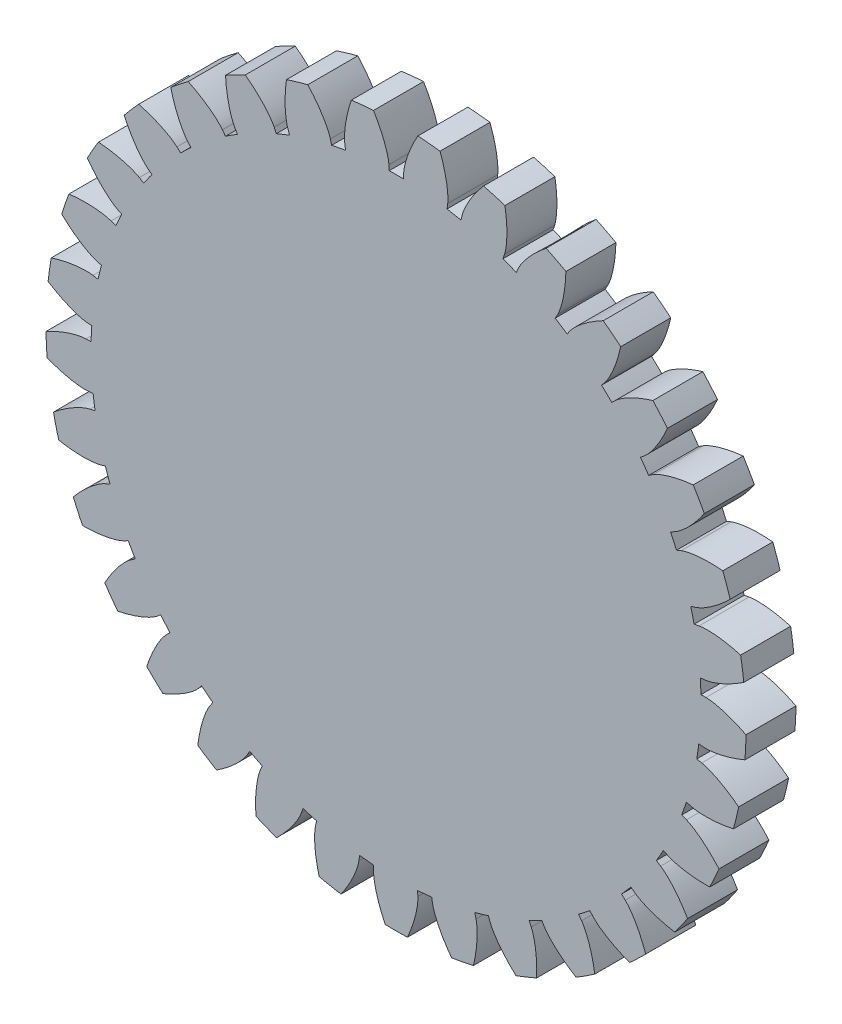
SolidWorks part; units mm, degrees
ref_plane "Спереди" through (0, 0, 0) normal (0, 0, 1) x (1, 0, 0)
ref_plane "Сверху" through (0, 0, 0) normal (0, 1, 0) x (1, 0, 0)
ref_plane "Справа" through (0, 0, 0) normal (1, 0, 0) x (0, 0, -1)
sketch "Эскиз2" plane through (0, 0, 0) normal (0, 0, 1) x (1, 0, 0)
  line L0 (0, 51.1792) -> (0, -43.95) construction
  line L1 (10.2103, 62.2838) -> (97.1798, 30.6294) construction
  line L2 (-13.5021, 66) -> (13.4511, 66) construction
  line L3 (1.5272, 62.0009) -> (1.4926, 60.9817)
  line L6 (-1.4156, 62.0036) -> (-1.3545, 60.985)
  circle A0 centre (0, 0) radius 70
  circle A1 centre (0, 0) radius 66 construction
  circle A2 centre (0, 0) radius 62.0197 construction
  circle A3 centre (0, 0) radius 61
  spline S0 degree 4 poles (1.5272, 62.0009) (1.529, 62.0517) (1.5344, 62.1533) (1.5532, 62.3559) (1.6041, 62.7397) (1.6972, 63.2512) (1.8619, 63.96) (2.1064, 64.81) (2.5522, 66.1188) (3.2996, 67.8941) (4.5374, 70.2843) (6.4126, 73.1886) (8.7564, 76.1773) (11.5565, 79.1636) (14.5826, 81.9194) (17.7987, 84.45) (21.3429, 86.8747) (25.9214, 89.5789) (31.6296, 92.3487) (38.5319, 94.9353) (46.4475, 97.0389) (53.5119, 98.2365) (59.6214, 98.8253) (64.7297, 99.035) (68.8201, 99.0381) (72.9067, 98.8812) (76.9854, 98.5675) (82.0635, 97.986) (88.1211, 96.9899) (95.1032, 95.4154) (101.4808, 93.5105) (106.2939, 91.812) (109.6398, 90.5071) (111.5036, 89.7481) (113.2806, 88.9869) (114.7009, 88.3604) (116.3483, 87.6041) (117.2223, 87.1924) (118.4723, 86.592) (119.4783, 86.0939) (120.646, 85.5087) (121.8873, 84.8664) (123.3709, 84.0795) (124.8011, 83.2956) (126.0714, 82.5816) (127.1351, 81.9677) (127.8524, 81.5474) (128.2039, 81.3388) (128.3825, 81.2327) knots 0 0 0 0 0 0.001401 0.002802 0.005604 0.010661 0.015718 0.022839 0.02996 0.048734 0.068727 0.096889 0.125051 0.153212 0.181374 0.209535 0.237696 0.271429 0.327752 0.384075 0.440398 0.496721 0.524883 0.553044 0.581206 0.609367 0.637529 0.66569 0.722013 0.778336 0.834659 0.84874 0.86282 0.876901 0.890982 0.900036 0.909091 0.920455 0.926136 0.931818 0.943182 0.954545 0.965909 0.977273 0.988636 0.994318 1 1 1 1 1 construction
  spline S1 degree 4 poles (1.5272, 62.0009) (1.529, 62.0517) (1.5344, 62.1533) (1.5532, 62.3559) (1.6041, 62.7397) (1.6972, 63.2512) (1.8619, 63.96) (2.1064, 64.81) (2.5522, 66.1188) (3.2996, 67.8941) (4.5374, 70.2843) (6.4126, 73.1886) (8.7564, 76.1773) (11.5565, 79.1636) (14.5826, 81.9194) (17.7987, 84.45) (21.3429, 86.8747) (25.9214, 89.5789) (31.6296, 92.3487) (38.5319, 94.9353) (46.4475, 97.0389) (53.5119, 98.2365) (59.6214, 98.8253) (64.7297, 99.035) (68.8201, 99.0381) (72.9067, 98.8812) (76.9854, 98.5675) (82.0635, 97.986) (88.1211, 96.9899) (95.1032, 95.4154) (101.4808, 93.5105) (106.2939, 91.812) (109.6398, 90.5071) (111.5036, 89.7481) (113.2806, 88.9869) (114.7009, 88.3604) (115.9185, 87.8014) (116.4592, 87.5498) (116.7297, 87.4228) knots 0 0 0 0 0 0.001401 0.002802 0.005604 0.010661 0.015718 0.022839 0.02996 0.048734 0.068727 0.096889 0.125051 0.153212 0.181374 0.209535 0.237696 0.271429 0.327752 0.384075 0.440398 0.496721 0.524883 0.553044 0.581206 0.609367 0.637529 0.66569 0.722013 0.778336 0.834659 0.84874 0.86282 0.876901 0.890982 0.900036 0.909091 0.909091 0.909091 0.909091 0.909091
  spline S2 degree 4 poles (-1.4156, 62.0036) (-1.4186, 62.0543) (-1.4267, 62.1557) (-1.4507, 62.3578) (-1.5115, 62.7401) (-1.6178, 63.2491) (-1.8008, 63.9533) (-2.0672, 64.7967) (-2.5466, 66.0936) (-3.3397, 67.849) (-4.6388, 70.2064) (-6.5884, 73.0613) (-9.0087, 75.9883) (-11.8851, 78.9013) (-14.9813, 81.578) (-18.2618, 84.0246) (-21.8675, 86.3569) (-26.5143, 88.9419) (-32.2922, 91.5632) (-39.259, 93.9705) (-47.2264, 95.8689) (-54.3194, 96.8834) (-60.4421, 97.3142) (-65.5541, 97.3917) (-69.6432, 97.2892) (-73.7244, 97.0267) (-77.7936, 96.6077) (-82.8549, 95.8951) (-88.8848, 94.7429) (-95.8238, 92.9884) (-102.1502, 90.9193) (-106.9177, 89.097) (-110.2288, 87.7061) (-112.0723, 86.8991) (-113.8291, 86.0922) (-115.2327, 85.4292) (-116.86, 84.6306) (-117.7231, 84.1964) (-118.9571, 83.5639) (-119.95, 83.04) (-121.1021, 82.4248) (-122.3264, 81.7506) (-123.7892, 80.9257) (-125.1987, 80.1051) (-126.45, 79.3585) (-127.4975, 78.7173) (-128.2037, 78.2786) (-128.5497, 78.061) (-128.7255, 77.9503) knots 0 0 0 0 0 0.001401 0.002802 0.005604 0.010661 0.015718 0.022839 0.02996 0.048734 0.068727 0.096889 0.125051 0.153212 0.181374 0.209535 0.237696 0.271429 0.327752 0.384075 0.440398 0.496721 0.524883 0.553044 0.581206 0.609367 0.637529 0.66569 0.722013 0.778336 0.834659 0.84874 0.86282 0.876901 0.890982 0.900036 0.909091 0.920455 0.926136 0.931818 0.943182 0.954545 0.965909 0.977273 0.988636 0.994318 1 1 1 1 1 construction
  spline S3 degree 4 poles (-1.4156, 62.0036) (-1.4186, 62.0543) (-1.4267, 62.1557) (-1.4507, 62.3578) (-1.5115, 62.7401) (-1.6178, 63.2491) (-1.8008, 63.9533) (-2.0672, 64.7967) (-2.5466, 66.0936) (-3.3397, 67.849) (-4.6388, 70.2064) (-6.5884, 73.0613) (-9.0087, 75.9883) (-11.8851, 78.9013) (-14.9813, 81.578) (-18.2618, 84.0246) (-21.8675, 86.3569) (-26.5143, 88.9419) (-32.2922, 91.5632) (-39.259, 93.9705) (-47.2264, 95.8689) (-54.3194, 96.8834) (-60.4421, 97.3142) (-65.5541, 97.3917) (-69.6432, 97.2892) (-73.7244, 97.0267) (-77.7936, 96.6077) (-82.8549, 95.8951) (-88.8848, 94.7429) (-95.8238, 92.9884) (-102.1502, 90.9193) (-106.9177, 89.097) (-110.2288, 87.7061) (-112.0723, 86.8991) (-113.8291, 86.0922) (-115.2327, 85.4292) (-116.4354, 84.8389) (-116.9695, 84.5735) (-117.2365, 84.4395) knots 0 0 0 0 0 0.001401 0.002802 0.005604 0.010661 0.015718 0.022839 0.02996 0.048734 0.068727 0.096889 0.125051 0.153212 0.181374 0.209535 0.237696 0.271429 0.327752 0.384075 0.440398 0.496721 0.524883 0.553044 0.581206 0.609367 0.637529 0.66569 0.722013 0.778336 0.834659 0.84874 0.86282 0.876901 0.890982 0.900036 0.909091 0.909091 0.909091 0.909091 0.909091
  point P9 (2.5133, 65.9521)
  point P12 (0, 0)
  point P13 (0, 0)
  point P18 (-2.5133, 65.9521)
  point P19 (0, 0)
  point P22 (0, 66)
  point P27 (-4.2145, 52.2185)
  dimension "D1" = 140
  dimension "D2" = 132
  dimension "D4" = 122
  dimension "D5" = 20
  dimension "D6" = 2.5133
  dimension "D7" = 2.5133
extrude "Бобышка-Вытянуть1" add sketch "Эскиз2" along normal blind 10 contours A0
extrude "Вырез-Вытянуть2" cut sketch "Эскиз2<4>" along normal through all contours S1 A0 L0 A3 region at (-0.0083, 66.4046, 0)
sketch "Эскиз2<4>" plane through (0, 0, 0) normal (0, 0, 1) x (1, 0, 0) same geometry as "Эскиз2"
pattern_circular "Круговой массив4" count 33 over 360 about axis through (0, 0, 10) along (0, 0, -1) of "Вырез-Вытянуть2"
equation "\"Модуль\" = 4мм"
equation "\"Число зубьев\"= 33"
equation "\"Диаметр делительной окружности\"= \"Модуль\" * \"Число зубьев\""
equation "\"Диаметр вершин\"= \"Модуль\" * ( \"Число зубьев\" + 2 )"
equation "\"Диаметр впадин\"= \"Модуль\" * ( \"Число зубьев\" - 2.5 )"
equation "\"Угол давления\"= 20градусов"
equation "\"Угол наклона\"= 0градусов"
equation "\"Диаметр основной окружности\"= \"Диаметр делительной окружности\" * cos ( \"Угол давления\" )"
equation "\"Смещение\"= 0"
equation "\"Зазор\"= \"Модуль\" * 0.1"
equation "\"Толщина зуба по хорде делительной окружности\"= pi * \"Модуль\" / 2 * \"Зазор\" + 2 * \"Смещение\" * tan ( \"Угол давления\" )"
equation "\"D1@Эскиз2\"=\"Диаметр вершин\""
equation "\"D2@Эскиз2\"=\"Диаметр делительной окружности\""
equation "\"D4@Эскиз2\"=\"Диаметр впадин\""
equation "\"D5@Эскиз2\"=\"Угол давления\""
equation "\"D6@Эскиз2\"= \"Толщина зуба по хорде делительной окружности\""
equation "\"D1@Круговой массив4\"=\"Число зубьев\""
equation "\"D7@Эскиз2\"=\"Толщина зуба по хорде делительной окружности\""
